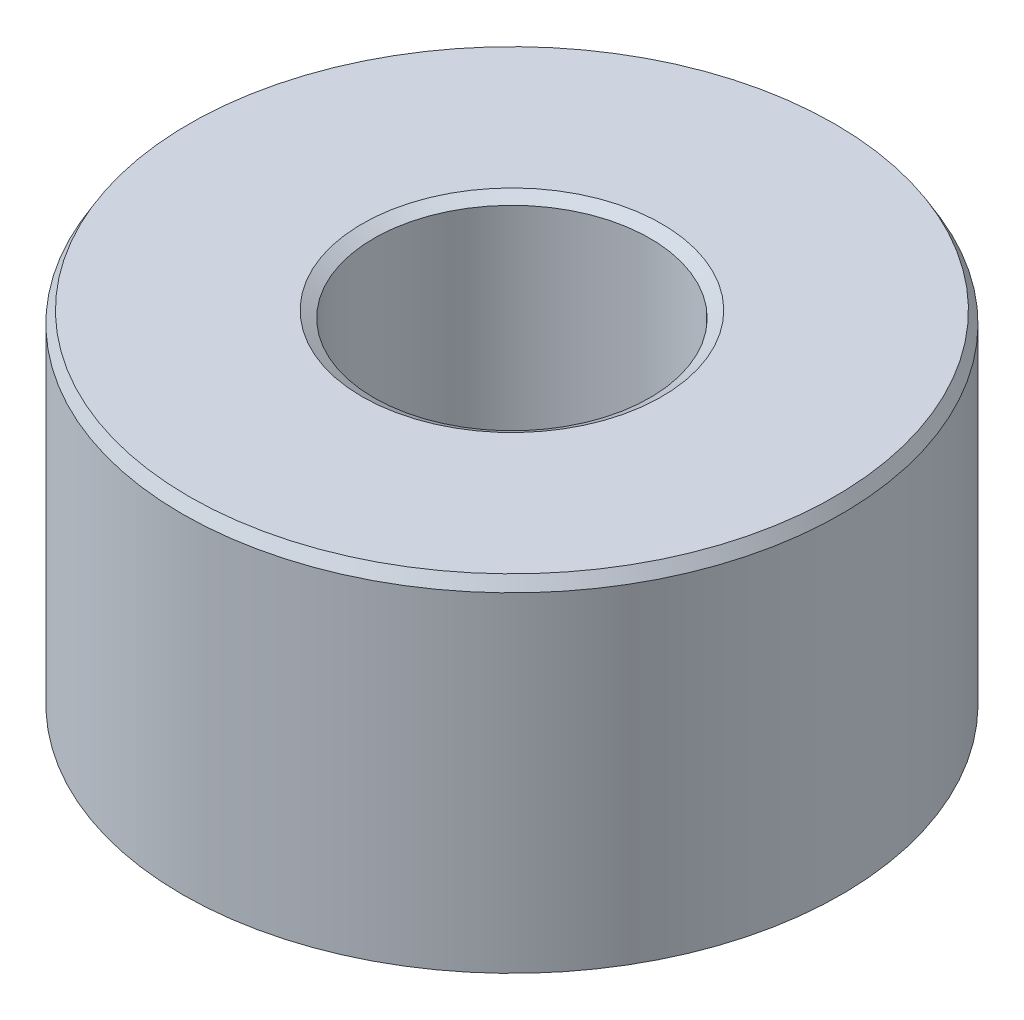
SolidWorks part; units mm, degrees
ref_plane "Front Plane" through (0, 0, 0) normal (0, 0, 1) x (1, 0, 0)
ref_plane "Top Plane" through (0, 0, 0) normal (0, 1, 0) x (1, 0, 0)
ref_plane "Right Plane" through (0, 0, 0) normal (1, 0, 0) x (0, 0, -1)
sketch "Sketch1" plane through (0, 0, 0) normal (0, 1, 0) x (1, 0, 0)
  circle A0 centre (0, 0) radius 60
  dimension "SLEEVE_OD" = 120
extrude "Boss-Extrude1" add sketch "Sketch1" along normal blind 63.3569
sketch "Sketch2" plane through (0, 0, 0) normal (0, 1, 0) x (1, 0, 0)
  circle A0 centre (0, 0) radius 25.1396
  dimension "BORE_D" = 50.2792
extrude "Cut-Extrude1" cut sketch "Sketch2" along normal through all
chamfer "Chamfer1" distance 2.1318 angle 30 4 edges at (0, 63.3569, 25.1396) (0, 0, 25.1396) (0, 0, 60) (0, 63.3569, 60) first distance on face at (0, 63.3569, 25.1396) first distance on face at (0, 0, 25.1396) first distance on face at (0, 63.3569, 60)
